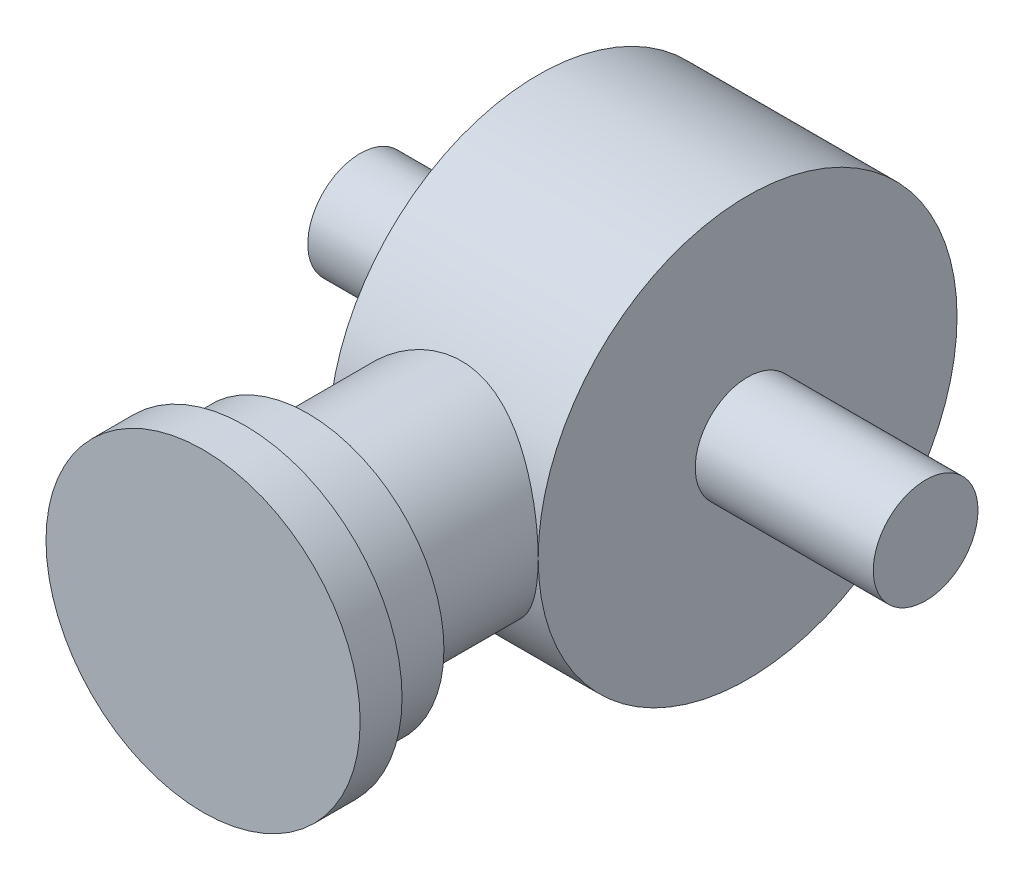
SolidWorks part; units mm, degrees
ref_plane "Alzado" through (0, 0, 0) normal (0, 0, 1) x (1, 0, 0)
ref_plane "Planta" through (0, 0, 0) normal (0, 1, 0) x (1, 0, 0)
ref_plane "Vista lateral" through (0, 0, 0) normal (1, 0, 0) x (0, 0, -1)
sketch "Croquis1" plane through (0, 0, 0) normal (1, 0, 0) x (0, 0, -1)
  circle A0 centre (0, 0) radius 25.4
  dimension "D1" = 50.8
extrude "Saliente-Extruir1" add sketch "Croquis1" along normal mid plane 25.4
ref_plane "Plano1" through (0, 0, 40.64) normal (0, 0, 1) x (1, 0, 0)
sketch "Croquis2" plane through (0, 0, 40.64) normal (0, 0, 1) x (1, 0, 0)
  circle A0 centre (0, 0) radius 12.7
extrude "Saliente-Extruir2" add sketch "Croquis2" against normal up to surface (15.24 mm away) up to face at (12.7, 0, -25.4)
sketch "Croquis3" plane through (0, 0, 40.64) normal (0, 0, 1) x (1, 0, 0)
  circle A0 centre (0, 0) radius 16.51
  dimension "D1" = 33.02
extrude "Saliente-Extruir3" add sketch "Croquis3" along normal blind 7.62
sketch "Croquis4" plane through (0, 0, 48.26) normal (0, 0, 1) x (1, 0, 0)
  circle A0 centre (0, 0) radius 19.05
  dimension "D1" = 38.1
extrude "Saliente-Extruir4" add sketch "Croquis4" along normal blind 5.08
sketch "Croquis6" plane through (0, 0, 0) normal (1, 0, 0) x (0, 0, -1)
  circle A0 centre (0, 0) radius 6.35
  dimension "D1" = 12.7
extrude "Saliente-Extruir5" add sketch "Croquis6" along normal mid plane 68.58
ref_axis "Axis1" through (34.29, 0, 0) along (-1, 0, 0)
ref_axis "Axis2" through (0, 0, 53.34) along (0, 0, -1)
ref_point "Point1"
ref_point "Point2"
